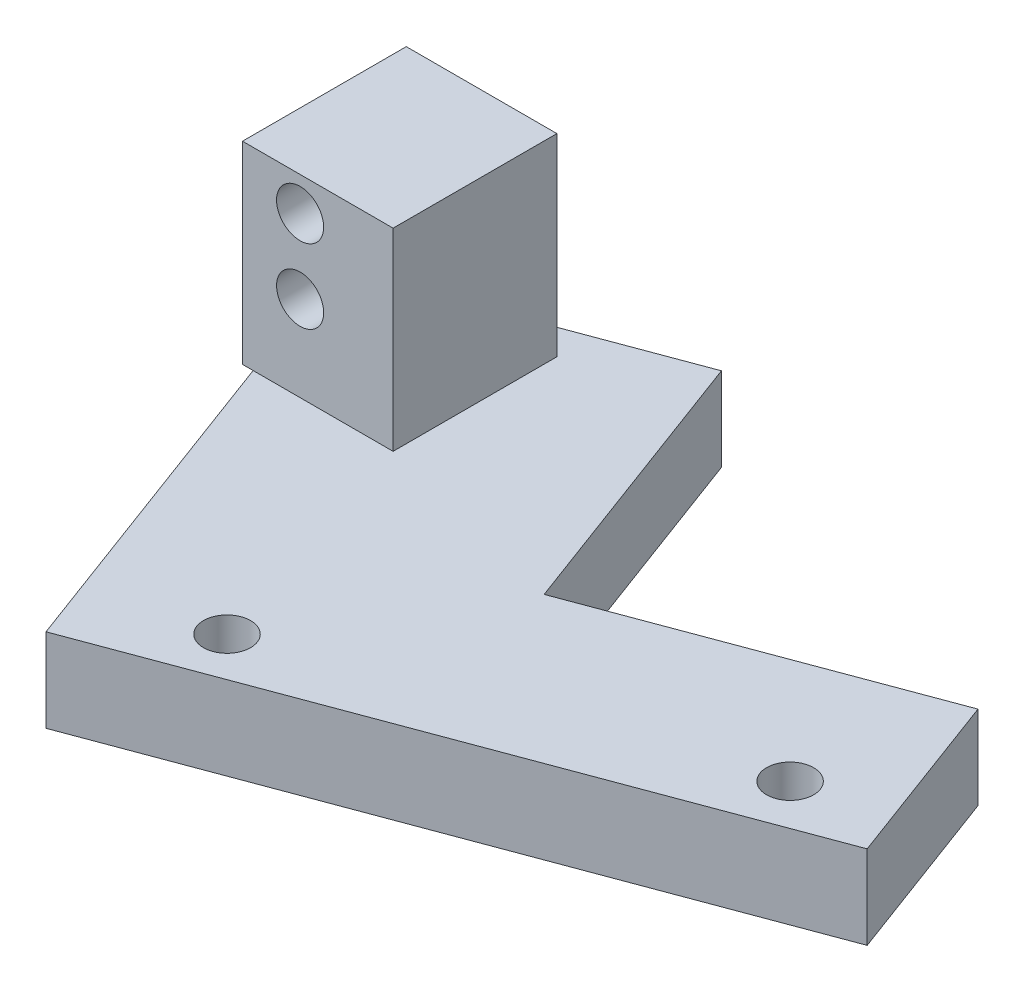
SolidWorks part; units mm, degrees
ref_plane "Front Plane" through (0, 0, 0) normal (0, 0, 1) x (1, 0, 0)
ref_plane "Top Plane" through (0, 0, 0) normal (0, 1, 0) x (1, 0, 0)
ref_plane "Right Plane" through (0, 0, 0) normal (1, 0, 0) x (0, 0, -1)
sketch "Sketch1" plane through (0, 0, 0) normal (0, 0, 1) x (1, 0, 0)
  line L0 (-111.8199, 128.5717) -> (-91.4999, 128.5717)
  line L1 (-122.8766, 128.5659) -> (-97.86, 128.5791) construction
  line L2 (-91.4999, 128.5717) -> (-91.4999, 102.49)
  line L3 (-91.4999, 102.49) -> (-111.8199, 102.49)
  line L4 (-111.8199, 102.49) -> (-111.8199, 128.5717)
  circle A0 centre (-104.0505, 124) radius 3.175
  circle A1 centre (-104.0452, 114) radius 3.175
  dimension "D4" = 6.35
  dimension "D5" = 6.35
  dimension "D1" = 20.32
  dimension "D2" = 6.35
  dimension "D3" = 3.81
extrude "Boss-Extrude1" add sketch "Sketch1" along normal up to surface (22.098 mm away)
ref_plane "Plane1" through (0, 102.49, 0) normal (0, 1, 0) x (1, 0, 0)
sketch "Sketch2" plane through (0, 102.49, 0) normal (0, 1, 0) x (1, 0, 0)
  line L4 (-91.4999, -22.098) -> (-111.8199, -22.098) construction
  line L6 (-93.8327, -66.5977) -> (-13.0724, -36.5641)
  line L9 (-116.8518, -4.6994) -> (-93.8327, -66.5977)
  line L10 (-116.8518, -4.6994) -> (-78.7605, 9.4662)
  line L11 (-78.7605, 9.4662) -> (-64.5949, -28.6251)
  line L12 (-64.5949, -28.6251) -> (-21.9259, -12.757)
  line L13 (-21.9259, -12.757) -> (-13.0724, -36.5641)
  circle A0 centre (-81.3473, -54.66) radius 3.175
  circle A1 centre (-26.1725, -33.8627) radius 3.175
  circle A2 centre (-81.3473, -54.66) radius 3.175 construction
  circle A3 centre (-26.1725, -33.8627) radius 3.175 construction
  dimension "D5" = 15.24
  dimension "D9" = 6.35
  dimension "D10" = 6.35
  dimension "D2" = 25.4
  dimension "D3" = 66.04
  dimension "D4" = 40.64
  dimension "D6" = 40.8958
  dimension "D7" = 86.164
  dimension "D8" = 69.601
extrude "Boss-Extrude2" add sketch "Sketch2" against normal up to surface (11.2786 mm away)
